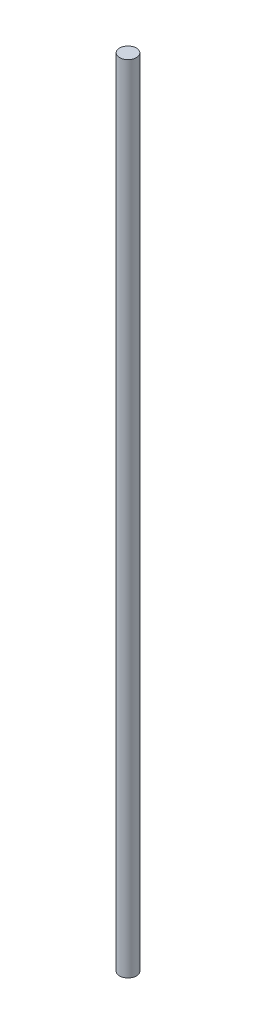
SolidWorks part; units mm, degrees
ref_plane "Front Plane" through (0, 0, 0) normal (0, 0, 1) x (1, 0, 0)
ref_plane "Top Plane" through (0, 0, 0) normal (0, 1, 0) x (1, 0, 0)
ref_plane "Right Plane" through (0, 0, 0) normal (1, 0, 0) x (0, 0, -1)
sketch "Sketch1" plane through (0, 0, 0) normal (0, 1, 0) x (1, 0, 0)
  circle A0 centre (0, 0) radius 6.35
  dimension "D1" = 12.7
extrude "Boss-Extrude1" add sketch "Sketch1" along normal mid plane 603.25
